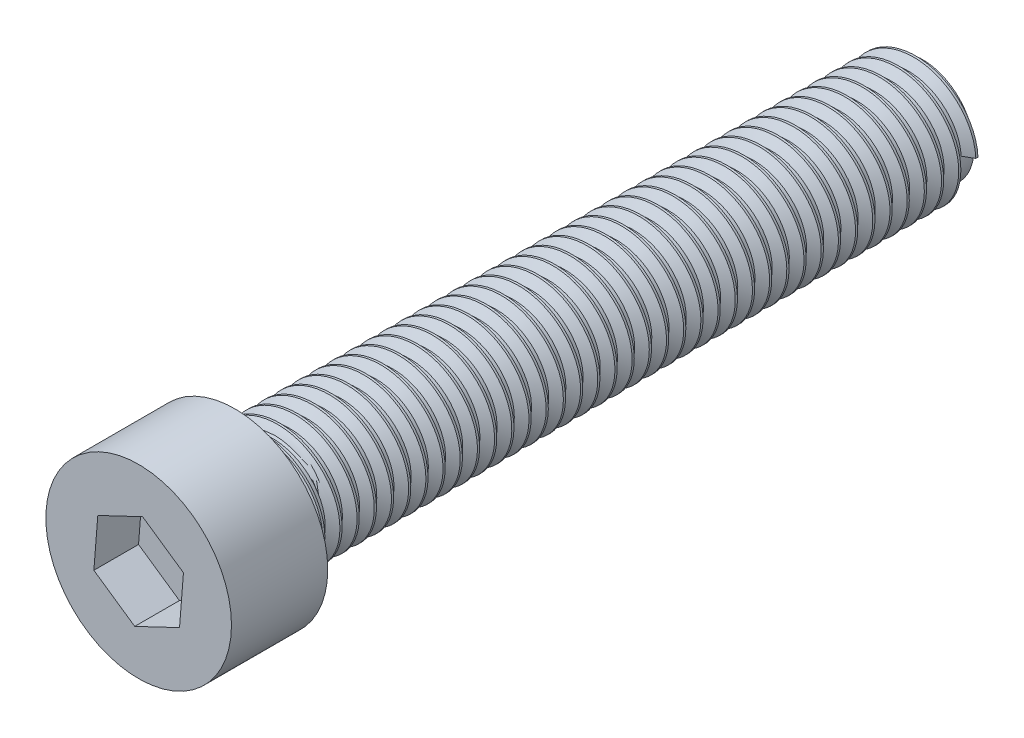
SolidWorks part; units mm, degrees
ref_plane "Front Plane" through (0, 0, 0) normal (0, 0, 1) x (1, 0, 0)
ref_plane "Top Plane" through (0, 0, 0) normal (0, 1, 0) x (1, 0, 0)
ref_plane "Right Plane" through (0, 0, 0) normal (1, 0, 0) x (0, 0, -1)
sketch "Sketch1" plane through (0, 0, 0) normal (0, 0, 1) x (1, 0, 0)
  circle A0 centre (0, 0) radius 2.7
  dimension "D1" = 5.4
extrude "Boss-Extrude1" add sketch "Sketch1" along normal blind 2.8
sketch "Sketch2" plane through (0, 0, 2.8) normal (0, 0, 1) x (1, 0, 0)
  line L1 (1.1889, -0.8184) -> (1.3032, 0.6204)
  line L2 (1.3032, 0.6204) -> (0.1143, 1.4388)
  line L3 (0.1143, 1.4388) -> (-1.1889, 0.8184)
  line L4 (-1.1889, 0.8184) -> (-1.3032, -0.6204)
  line L5 (-1.3032, -0.6204) -> (-0.1143, -1.4388)
  line L6 (-0.1143, -1.4388) -> (1.1889, -0.8184)
  circle A0 centre (0, 0) radius 1.25 construction
  dimension "D1" = 2.5
extrude "Cut-Extrude1" cut sketch "Sketch2" against normal blind 1.3
sketch "Sketch3" plane through (0, 0, 0) normal (0, 0, -1) x (-1, 0, 0)
  circle A0 centre (0, 0) radius 1.5
  dimension "D1" = 3
extrude "Boss-Extrude2" add sketch "Sketch3" along normal blind 20
thread "Thread1" pitch 0.5 profile "Thread Profile1" start angle 0, offset 0, length 0, pitch 0.5, diameter 3
ref_plane "Plane1" through (1.5, 0, -20) normal (0, -1, 0) x (1, 0, 0)
sketch "Thread Profile1" plane through (1.5, 0, -20) normal (0, -1, 0) x (1, 0, 0)
  line L0 (0, 0) -> (0, 0.5) construction
  line L1 (0, 0) -> (0.2706, 0.1562)
  line L2 (0.2706, 0.1562) -> (0.2706, 0.2187)
  line L3 (0.2706, 0.2187) -> (0, 0.375)
  line L4 (0.2706, 0.1875) -> (0, 0.1875) construction
  line L11 (0, 0) -> (0, 0.375)
  point P2 (0, 0)
  dimension "Pitch" = 0.5
  dimension "Profile_Angle" = 60
  dimension "Profile_Land" = 0.0625
  dimension "Profile_Height" = 0.2706
